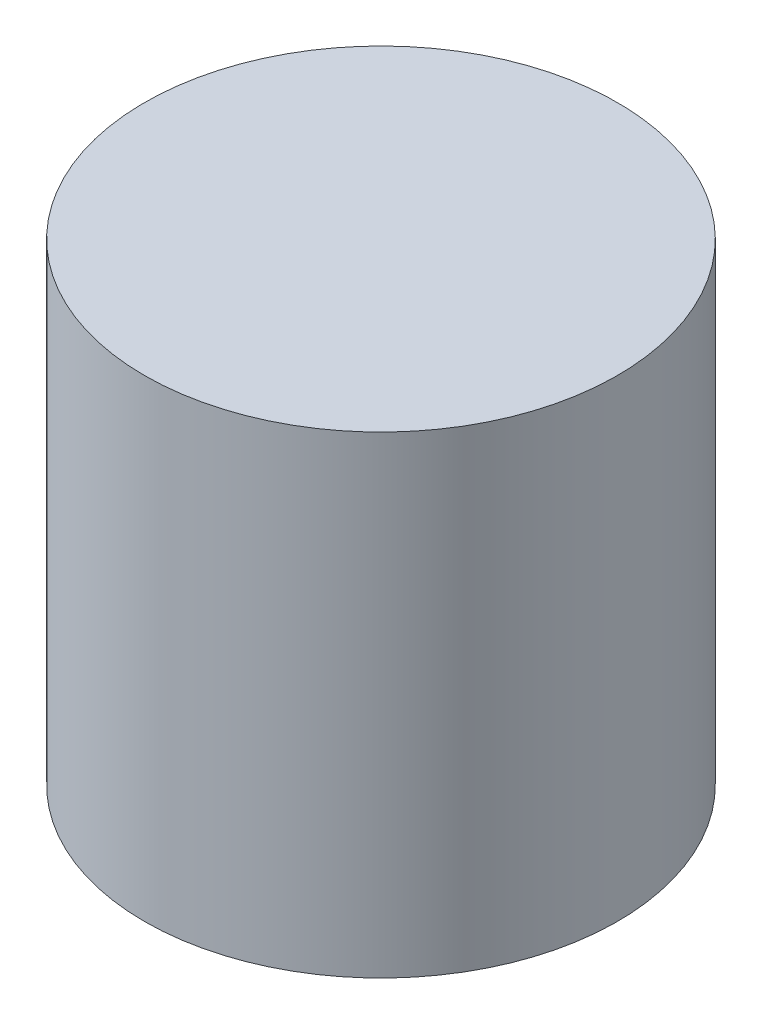
SolidWorks part; units mm, degrees
ref_plane "Front" through (0, 0, 0) normal (0, 0, 1) x (1, 0, 0)
ref_plane "Top" through (0, 0, 0) normal (0, 1, 0) x (1, 0, 0)
ref_plane "Right" through (0, 0, 0) normal (1, 0, 0) x (0, 0, -1)
sketch "Sketch1" plane through (0, 0, 0) normal (0, 1, 0) x (1, 0, 0)
  circle A0 centre (0, 0) radius 3.175
  dimension "D1" = 6.35
extrude "Boss-Extrude1" add sketch "Sketch1" along normal blind 6.35
